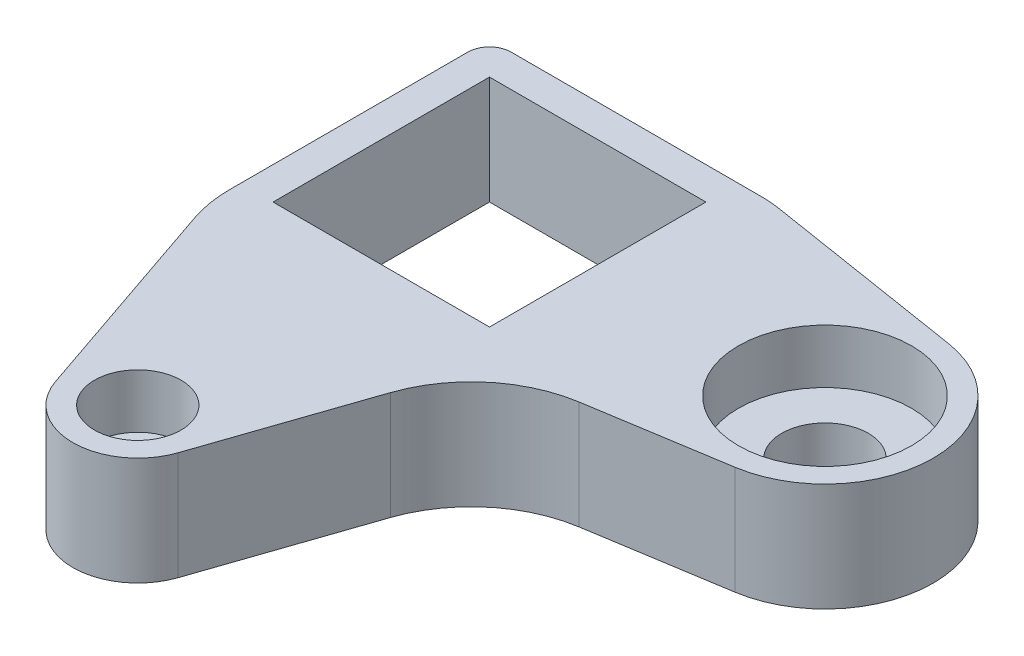
SolidWorks part; units mm, degrees
ref_plane "Front Plane" through (0, 0, 0) normal (0, 0, 1) x (1, 0, 0)
ref_plane "Top Plane" through (0, 0, 0) normal (0, 1, 0) x (1, 0, 0)
ref_plane "Right Plane" through (0, 0, 0) normal (1, 0, 0) x (0, 0, -1)
sketch "Sketch1" plane through (0, 0, 0) normal (0, 1, 0) x (1, 0, 0)
  line L0 (20, 0) -> (41, -10) construction
  line L1 (10, -42.5) -> (0, -20) construction
  line L2 (41, -10) -> (20, -20) construction
  line L3 (0, 0) -> (0, -20) construction
  line L4 (0, 0) -> (20, -20) construction
  line L5 (23.9399, 2.85) -> (42.5764, -0.125)
  line L12 (-3, -23) -> (23, -23) construction
  line L13 (0, 0) -> (20, 0) construction
  line L14 (0, 0) -> (0, -20) construction
  line L15 (0, -20) -> (20, -20) construction
  line L16 (20, 0) -> (20, -20) construction
  line L17 (10, -42.5) -> (20, -20) construction
  line L18 (-3, -21.0074) -> (-3, 1)
  line L19 (-1, 3) -> (22.0482, 3)
  line L20 (23, -23) -> (23, 3) construction
  line L21 (-3, -23) -> (23, 3) construction
  line L22 (-3, 3) -> (23, -23) construction
  line L23 (0, -20) -> (20, -20)
  line L24 (0, -20) -> (0, 0)
  line L25 (0, 0) -> (20, 0)
  line L26 (20, -20) -> (20, 0)
  line L27 (0, -20) -> (20, 0) construction
  line L28 (0, 0) -> (20, -20) construction
  line L29 (30.1306, -21.8617) -> (42.5764, -19.875)
  line L30 (20.6662, -29.8333) -> (15.678, -44.4392)
  line L31 (-2.356, -24.8857) -> (4.322, -44.4392)
  circle A4 centre (10, -42.5) radius 4 construction
  circle A5 centre (41, -10) radius 4 construction
  arc A6 (-3, 1) -> (-1, 3) centre (-1, 1) cw
  circle A7 centre (41, -10) radius 8 construction
  arc A8 (42.5764, -19.875) -> (42.5764, -0.125) centre (41, -10) ccw
  arc A9 (4.322, -44.4392) -> (15.678, -44.4392) centre (10, -42.5) ccw
  arc A10 (30.1306, -21.8617) -> (20.6662, -29.8333) centre (32.0222, -33.7117) ccw
  arc A11 (23.9399, 2.85) -> (22.0482, 3) centre (22.0482, -9) ccw
  arc A12 (-3, -21.0074) -> (-2.356, -24.8857) centre (9, -21.0074) ccw
  point P0 (10, -10)
  point P10 (10, -10)
  dimension "D6" = 8
  dimension "D7" = 16
  dimension "D8" = 20
  dimension "D9" = 12
  dimension "D10" = 12
  dimension "D11" = 12
  dimension "D5" = 2
  dimension "D2" = 20
  dimension "D3" = 3
  dimension "D4" = 42.5
  dimension "D12" = 20
  dimension "D13" = 41
extrude "Boss-Extrude1" add sketch "Sketch1" along normal blind 10
ref_plane "Plane1" through (0, 5, 0) normal (0, 1, 0) x (1, 0, 0)
sketch "Sketch2" plane through (0, 5, 0) normal (0, 1, 0) x (1, 0, 0)
  line L0 (20, 0) -> (41, -10) construction
  line L1 (10, -42.5) -> (0, -20) construction
  line L2 (41, -10) -> (20, -20) construction
  line L3 (0, 0) -> (0, -20) construction
  line L4 (0, 0) -> (20, -20) construction
  line L5 (23.9399, 2.85) -> (42.5764, -0.125) construction
  line L6 (-3, -23) -> (23, -23) construction
  line L7 (0, 0) -> (20, 0) construction
  line L8 (0, 0) -> (0, -20) construction
  line L9 (0, -20) -> (20, -20) construction
  line L10 (20, 0) -> (20, -20) construction
  line L11 (10, -42.5) -> (20, -20) construction
  line L12 (-3, -21.0074) -> (-3, 1) construction
  line L13 (-1, 3) -> (22.0482, 3) construction
  line L14 (23, -23) -> (23, 3) construction
  line L15 (-3, -23) -> (23, 3) construction
  line L16 (-3, 3) -> (23, -23) construction
  line L17 (0, -20) -> (20, -20) construction
  line L18 (0, -20) -> (0, 0) construction
  line L19 (0, 0) -> (20, 0) construction
  line L20 (20, -20) -> (20, 0) construction
  line L21 (0, -20) -> (20, 0) construction
  line L22 (0, 0) -> (20, -20) construction
  line L23 (30.1306, -21.8617) -> (42.5764, -19.875) construction
  line L24 (20.6662, -29.8333) -> (15.678, -44.4392) construction
  line L25 (-2.356, -24.8857) -> (4.322, -44.4392) construction
  circle A0 centre (10, -42.5) radius 4 construction
  circle A1 centre (41, -10) radius 4
  arc A2 (-3, 1) -> (-1, 3) centre (-1, 1) cw construction
  circle A3 centre (41, -10) radius 8 construction
  arc A4 (42.5764, -19.875) -> (42.5764, -0.125) centre (41, -10) ccw construction
  arc A5 (4.322, -44.4392) -> (15.678, -44.4392) centre (10, -42.5) ccw construction
  arc A6 (30.1306, -21.8617) -> (20.6662, -29.8333) centre (32.0222, -33.7117) ccw construction
  arc A7 (23.9399, 2.85) -> (22.0482, 3) centre (22.0482, -9) ccw construction
  arc A8 (-3, -21.0074) -> (-2.356, -24.8857) centre (9, -21.0074) ccw construction
  point P0 (10, -10)
  point P10 (10, -10)
  dimension "D2" = 8
  dimension "D7" = 2
  dimension "D8" = 16
  dimension "D9" = 20
  dimension "D10" = 12
  dimension "D11" = 12
  dimension "D12" = 12
  dimension "D1" = 20
  dimension "D3" = 20
  dimension "D4" = 41
  dimension "D5" = 42.5
  dimension "D6" = 3
extrude "Cut-Extrude2" cut sketch "Sketch2" against normal blind 68
sketch "Sketch3" plane through (0, 5, 0) normal (0, 1, 0) x (1, 0, 0)
  line L0 (20, 0) -> (41, -10) construction
  line L1 (10, -42.5) -> (0, -20) construction
  line L2 (41, -10) -> (20, -20) construction
  line L3 (0, 0) -> (0, -20) construction
  line L4 (0, 0) -> (20, -20) construction
  line L5 (23.9399, 2.85) -> (42.5764, -0.125) construction
  line L6 (-3, -23) -> (23, -23) construction
  line L7 (0, 0) -> (20, 0) construction
  line L8 (0, 0) -> (0, -20) construction
  line L9 (0, -20) -> (20, -20) construction
  line L10 (20, 0) -> (20, -20) construction
  line L11 (10, -42.5) -> (20, -20) construction
  line L12 (-3, -21.0074) -> (-3, 1) construction
  line L13 (-1, 3) -> (22.0482, 3) construction
  line L14 (23, -23) -> (23, 3) construction
  line L15 (-3, -23) -> (23, 3) construction
  line L16 (-3, 3) -> (23, -23) construction
  line L17 (0, -20) -> (20, -20) construction
  line L18 (0, -20) -> (0, 0) construction
  line L19 (0, 0) -> (20, 0) construction
  line L20 (20, -20) -> (20, 0) construction
  line L21 (0, -20) -> (20, 0) construction
  line L22 (0, 0) -> (20, -20) construction
  line L23 (30.1306, -21.8617) -> (42.5764, -19.875) construction
  line L24 (20.6662, -29.8333) -> (15.678, -44.4392) construction
  line L25 (-2.356, -24.8857) -> (4.322, -44.4392) construction
  circle A0 centre (10, -42.5) radius 4
  circle A1 centre (41, -10) radius 4 construction
  arc A2 (-3, 1) -> (-1, 3) centre (-1, 1) cw construction
  circle A3 centre (41, -10) radius 8
  arc A4 (42.5764, -19.875) -> (42.5764, -0.125) centre (41, -10) ccw construction
  arc A5 (4.322, -44.4392) -> (15.678, -44.4392) centre (10, -42.5) ccw construction
  arc A6 (30.1306, -21.8617) -> (20.6662, -29.8333) centre (32.0222, -33.7117) ccw construction
  arc A7 (23.9399, 2.85) -> (22.0482, 3) centre (22.0482, -9) ccw construction
  arc A8 (-3, -21.0074) -> (-2.356, -24.8857) centre (9, -21.0074) ccw construction
  point P0 (10, -10)
  point P10 (10, -10)
  dimension "D2" = 8
  dimension "D7" = 2
  dimension "D8" = 16
  dimension "D9" = 20
  dimension "D10" = 12
  dimension "D11" = 12
  dimension "D12" = 12
  dimension "D1" = 20
  dimension "D3" = 20
  dimension "D4" = 41
  dimension "D5" = 42.5
  dimension "D6" = 3
extrude "Cut-Extrude3" cut sketch "Sketch3" along normal blind 70
